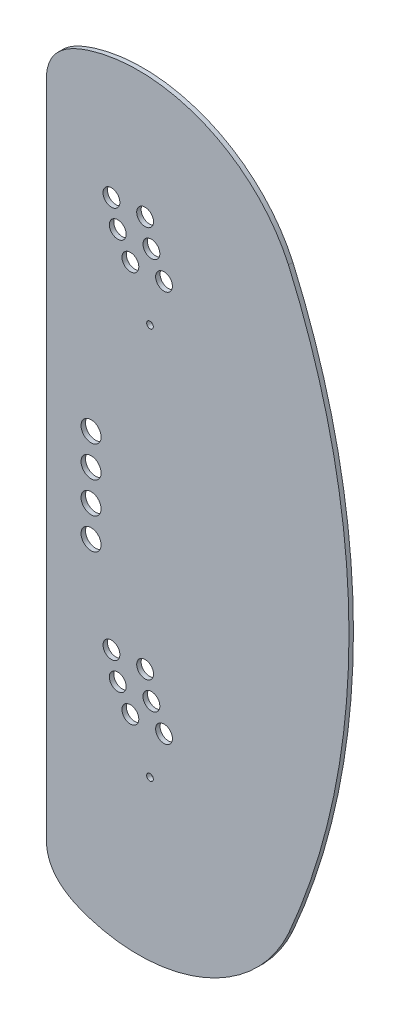
SolidWorks part; units mm, degrees
material "Acrylic (Medium-high impact)"
ref_plane "Front Plane" through (0, 0, 0) normal (0, 0, 1) x (1, 0, 0)
ref_plane "Top Plane" through (0, 0, 0) normal (0, 1, 0) x (1, 0, 0)
ref_plane "Right Plane" through (0, 0, 0) normal (1, 0, 0) x (0, 0, -1)
sketch "Sketch1" plane through (0, 0, 0) normal (0, 0, 1) x (1, 0, 0)
  line L95 (1361.0966, 1948.8635) -> (1361.0966, 996.3635)
  arc A0 (1706.2361, 1059.6777) -> (1706.2361, 1885.5492) centre (761.2616, 1472.6135) ccw
  circle A3 centre (1510.6649, 1248.8146) radius 12
  circle A7 centre (1462.6649, 1248.8145) radius 12
  circle A9 centre (1508.6644, 1153.8145) radius 4.7625
  circle A19 centre (1508.6644, 1712.6145) radius 4.7625
  circle A20 centre (1453.6649, 1283.8145) radius 12
  circle A21 centre (1528.6649, 1217.5646) radius 12
  circle A24 centre (1480.665, 1217.5646) radius 12
  circle A28 centre (1501.6649, 1283.8145) radius 12
  circle A29 centre (1424.5966, 1539.2885) radius 14.2875
  circle A30 centre (1424.5966, 1494.8385) radius 14.2875
  circle A31 centre (1424.5966, 1450.3885) radius 14.2875
  circle A32 centre (1424.5966, 1405.9385) radius 14.2875
  circle A40 centre (1501.6649, 1842.6145) radius 12
  circle A41 centre (1510.6649, 1807.6146) radius 12
  circle A42 centre (1528.6649, 1776.3646) radius 12
  circle A43 centre (1462.665, 1807.6146) radius 12
  circle A44 centre (1480.6649, 1776.3646) radius 12
  circle A45 centre (1453.665, 1842.6145) radius 12
  spline S1 degree 3 poles (1361.0966, 996.3635) (1364.4008, 961.2038) (1498.6132, 888.7647) (1658.3076, 954.5721) (1706.2361, 1059.6777) knots 0 0 0 0 0.219674 1 1 1 1
  spline S2 degree 3 poles (1361.0966, 1948.8635) (1364.4008, 1984.0232) (1498.6132, 2056.4623) (1658.3076, 1990.6549) (1706.2361, 1885.5492) knots 0 0 0 0 0.219674 1 1 1 1
extrude "Boss-Extrude1" add sketch "Sketch1" along normal blind 6.35 contours S2 L95 S1 A0 A45 A44 A43 A42 A41 A40 A32 A31 A30 A29 A28 A24 A21 A20 A19 A9 A7 A3 region at (1556.4391, 1471.8505, 0)
